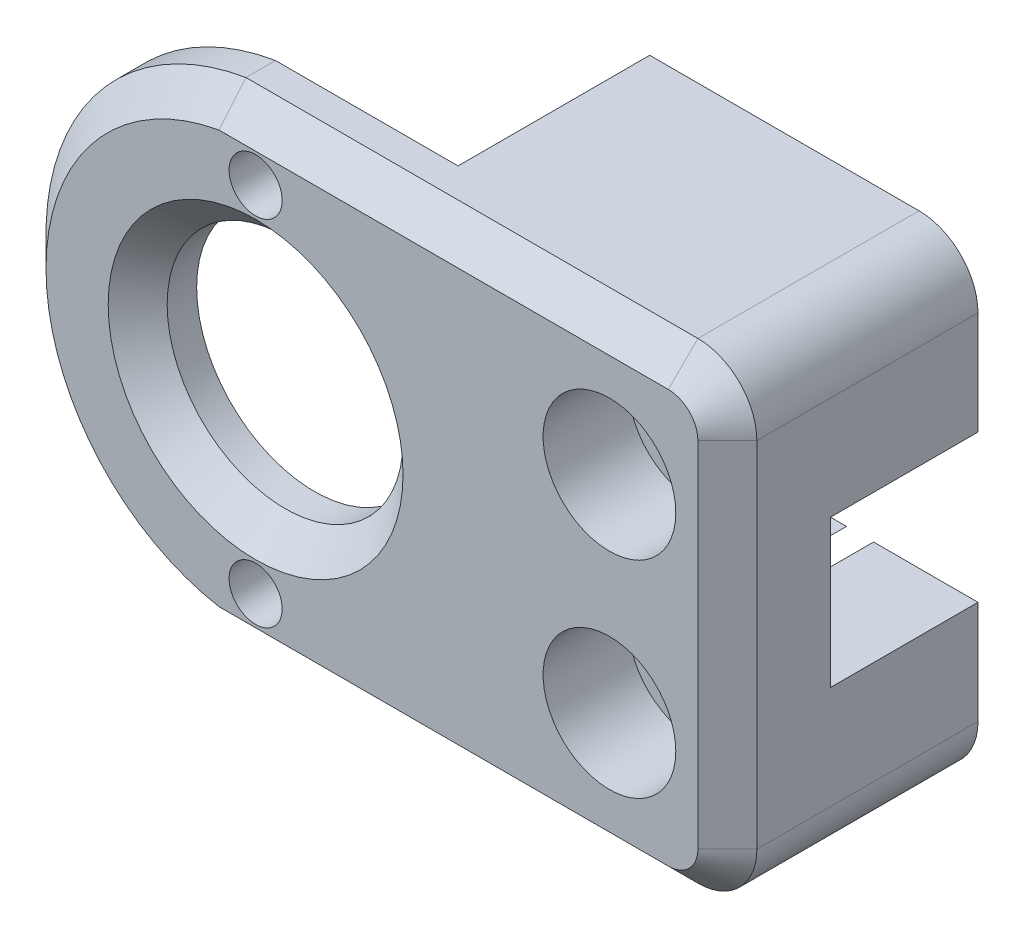
SolidWorks part; units mm, degrees
ref_plane "Alzado" through (0, 0, 0) normal (0, 0, 1) x (1, 0, 0)
ref_plane "Planta" through (0, 0, 0) normal (0, 1, 0) x (1, 0, 0)
ref_plane "Vista lateral" through (0, 0, 0) normal (1, 0, 0) x (0, 0, -1)
sketch "Croquis1" plane through (0, 0, 0) normal (0, 0, 1) x (1, 0, 0)
  line L0 (0, 0) -> (7143.243, 0) construction
  line L1 (0, 0) -> (0, 7143.243) construction
  line L3 (-1.3266, 8) -> (16, 8)
  line L4 (16, 8) -> (16, 0)
  line L5 (16, 0) -> (8, 0)
  line L6 (8, 0) -> (8, 4.1231) construction
  line L8 (10.8753, 7) -> (-12.9398, 7) construction
  line L9 (5.6569, 7) -> (8, 4.1231) construction
  line L10 (-8.1093, 0) -> (8, 0)
  circle A0 centre (0, 6) radius 0.9
  circle A2 centre (12, 3.5) radius 1.1
  circle A3 centre (0, 0) radius 9 construction
  arc A4 (-1.3266, 8) -> (-8.1093, 0) centre (0, 0) ccw
  dimension "D1" = 6
  dimension "1,8" = 1.8
  dimension "D5" = 7
  dimension "2,2" = 2.2
  dimension "D7" = 18
  dimension "D3" = 8
  dimension "D6" = 12
  dimension "8" = 8
  dimension "D8" = 7
  dimension "D9" = 16
extrude "Saliente-Extruir1" add sketch "Croquis1" along normal blind 8.5
fillet "Redondeo1" radius 2 1 edges at (16, 8, 4.25)
sketch "Croquis4" plane through (0, 0, 0) normal (0, 0, -1) x (-1, 0, 0)
  line L2 (-5.6569, 7) -> (-8, 4.1231)
  line L3 (-8, 4.1231) -> (-8, 0)
  line L4 (-8, 0) -> (8.1093, 0)
  line L7 (200000, 0) -> (-207143.243, 0) construction
  line L8 (8.1093, 0) -> (9, 0)
  arc A2 (-5.6569, 7) -> (9, 0) centre (0, 0) cw
extrude "Cortar-Extruir6" cut sketch "Croquis4" along direction (0, 0, 1) on the side against the normal offset from surface (6.5 mm away) 2 up to face at (0.9, 6, 8.5)
chamfer "Chaflán1" distance 1 angle 45 5 edges at (-6.1854, 5.2441, 8.5) (6.3367, 8, 8.5) (4.1231, 8, 3.25) (16, 3, 8.5) (15.4142, 7.4142, 8.5) first distance on face at (-5.4517, 4.6221, 7.5) first distance on face at (5.5988, 8, 5) first distance on face at (4.9027, 7.5196, 3.25) first distance on face at (16, 3, 4.25) first distance on face at (15.2071, 7.2071, 4.25)
sketch "Croquis5" plane through (0, 0, 0) normal (0, 0, -1) x (-1, 0, 0)
  line L0 (-8, 0) -> (-8, 4.1231) construction
  line L1 (-16, 0) -> (-8, 0)
  line L2 (-16, 0) -> (-16, 2.5)
  line L3 (-16, 2.5) -> (-8, 2.5)
  line L4 (-8, 0) -> (-8, 2.5)
  line L5 (-16, 0) -> (-8, 2.5) construction
  line L6 (-16, 2.5) -> (-8, 0) construction
  point P4 (-12, 1.25)
  dimension "D1" = 2.5
extrude "Cortar-Extruir7" cut sketch "Croquis5" against normal offset from surface (5 mm away) 1.5 up to face at (0.9, 6, 6.5)
sketch "Croquis6" plane through (0, 0, 8.5) normal (0, 0, 1) x (1, 0, 0)
  circle A0 centre (12, 3.5) radius 2.25
  dimension "D1" = 4.5
extrude "Cortar-Extruir8" cut sketch "Croquis6" against normal offset from surface (2.9 mm away) 0.6 up to face at (12, 1.65, 5)
chamfer "Chaflán3" distance 0.2 angle 45 1 edges at (0.9, 6, 6.5)
mirror "Simetría1" about plane through (16, 0, 8.5) normal (0, 1, 0) of bodies 108 101
sketch "Croquis7" plane through (0, 0, 8.5) normal (0, 0, 1) x (1, 0, 0)
  circle A0 centre (0, 0) radius 4
  dimension "D1" = 8
extrude "Cortar-Extruir9" cut sketch "Croquis7" against normal through all
chamfer "Chaflán2" distance 1 angle 45 1 edges at (4, 0, 8.5)
